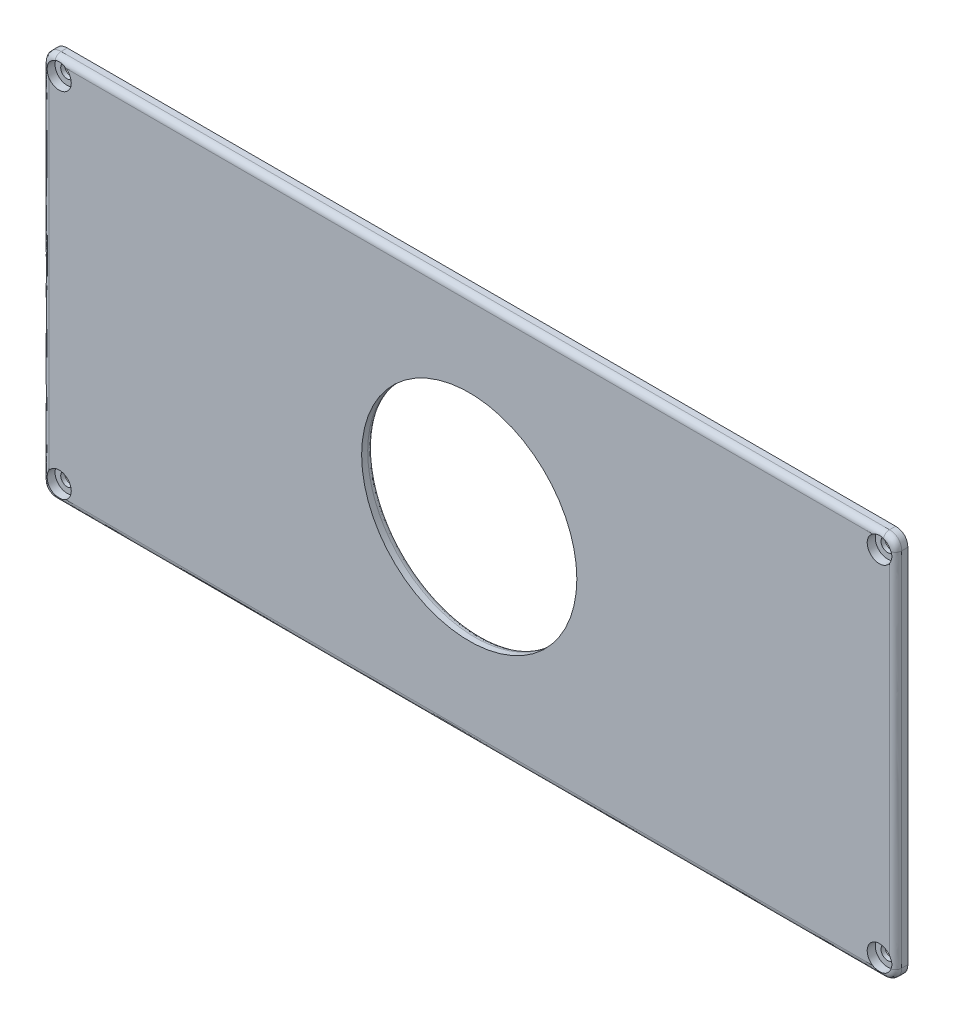
SolidWorks part; units mm, degrees
ref_plane "前视基准面" through (0, 0, 0) normal (0, 0, 1) x (1, 0, 0)
ref_plane "上视基准面" through (0, 0, 0) normal (0, 1, 0) x (1, 0, 0)
ref_plane "右视基准面" through (0, 0, 0) normal (1, 0, 0) x (0, 0, -1)
sketch "草图1" plane through (0, 0, 0) normal (0, 0, 1) x (1, 0, 0)
  line L0 (0, 0) -> (0, 47.5) construction
  line L1 (-105, 47.5) -> (105, 47.5)
  line L2 (-105, 47.5) -> (-105, -47.5)
  line L3 (-105, -47.5) -> (105, -47.5)
  line L4 (105, 47.5) -> (105, -47.5)
  line L5 (-105, 47.5) -> (105, -47.5) construction
  line L6 (-105, -47.5) -> (105, 47.5) construction
  line L7 (0, 0) -> (105, 0) construction
  circle A0 centre (-101, 43.5) radius 1.6
  circle A1 centre (101, 43.5) radius 1.6
  circle A2 centre (101, -43.5) radius 1.6
  circle A3 centre (-101, -43.5) radius 1.6
  circle A4 centre (0, 0) radius 26.5
  point P0 (0, 0)
  dimension "D3" = 4
  dimension "D1" = 210
  dimension "D2" = 95
  dimension "D4" = 4
extrude "凸台-拉伸1" add sketch "草图1" along normal blind 3
fillet "圆角3" radius 1.5 1 edges at (26.5, 0, 0) conic rho 0.45
fillet "圆角4" radius 3 4 edges at (105, -47.5, 1.5) (105, 47.5, 1.5) (-105, 47.5, 1.5) (-105, -47.5, 1.5) conic rho 0.45
fillet "圆角5" radius 1.5 8 edges conic rho 0.45
sketch "草图2" plane through (0, 0, 3) normal (0, 0, 1) x (1, 0, 0)
  circle A0 centre (-101, 43.5) radius 3
  circle A1 centre (101, 43.5) radius 3
  circle A2 centre (101, -43.5) radius 3
  circle A3 centre (-101, -43.5) radius 3
extrude "切除-拉伸1" cut sketch "草图2" against normal blind 2
